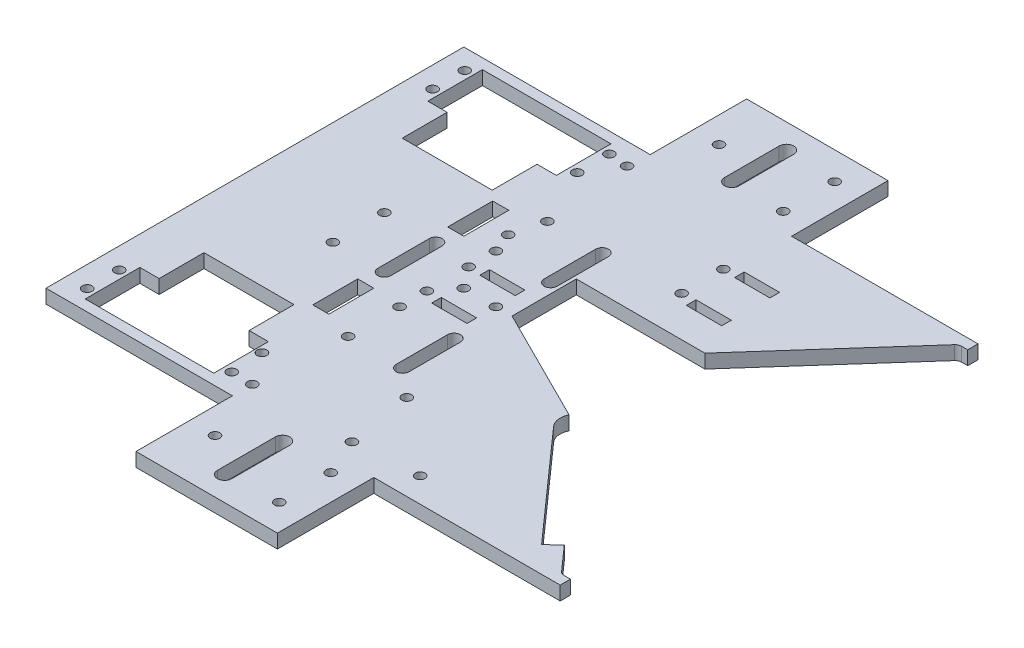
SolidWorks part; units mm, degrees
material "Acrylic (Medium-high impact)"
ref_plane "Front Plane" through (0, 0, 0) normal (0, 0, 1) x (1, 0, 0)
ref_plane "Top Plane" through (0, 0, 0) normal (0, 1, 0) x (1, 0, 0)
ref_plane "Right Plane" through (0, 0, 0) normal (1, 0, 0) x (0, 0, -1)
sketch "Sketch2" plane through (0, 0, 0) normal (0, 1, 0) x (1, 0, 0)
  line L2 (0, 0) -> (0, 65)
  line L3 (0, 65) -> (58, 65)
  line L4 (160, 0) -> (160, 65)
  line L8 (0, 0) -> (160, 0)
  line L9 (102, 65) -> (160, 65)
  line L11 (102, 65) -> (102, 95)
  line L12 (58, 65) -> (58, 95)
  line L13 (58, 95) -> (102, 95)
  dimension "D1" = 65
  dimension "D2" = 160
  dimension "D3" = 44
  dimension "D4" = 30
extrude "Boss-Extrude1" add sketch "Sketch2" along normal blind 4.3
mirror "Mirror1" about plane through (0, 4.3, 0) normal (0, 0, -1) of bodies 101
sketch "Sketch3" plane through (0, 4.3, 0) normal (0, 1, 0) x (1, 0, 0)
  line L0 (160, 61.8) -> (160, -61.8)
  line L1 (120.0126, 20) -> (157.1565, 61.8)
  line L3 (80.0126, 0) -> (80.0126, 20)
  line L4 (80.0126, 20) -> (120.0126, 20)
  line L12 (160, 65) -> (102, 65)
  line L13 (102, 65) -> (102, 95)
  line L15 (102, 95) -> (58, 95)
  line L16 (58, 65) -> (0, 65)
  line L17 (0, 65) -> (0, -65)
  line L18 (0, -65) -> (58, -65)
  line L20 (58, 95) -> (58, 65)
  line L22 (102, -65) -> (160, -65)
  line L23 (160, -65) -> (160, 65)
  line L36 (58, -65) -> (58, -95)
  line L38 (58, -95) -> (102, -95)
  line L39 (58, -95) -> (102, -95)
  line L40 (102, -95) -> (102, -65)
  line L42 (160, -61.8) -> (157.1556, -61.8)
  line L45 (160, 61.8) -> (157.1565, 61.8)
  line L48 (80.0126, 0) -> (120, -20)
  line L49 (120, -20) -> (157.1556, -61.8)
  line M24 (160, -65) -> (160, 65)
  dimension "D2" = 130
  dimension "D3" = 20
  dimension "D4" = 40
  dimension "D1" = 0
extrude "Cut-Extrude1" cut sketch "Sketch3" against normal blind 4.5 contours L48 L49 L1 L4 L3 M24 region at (132.7054, 4.3, -1.1594)
fillet "Fillet1" radius 2 2 edges at (157.1565, 2.15, -61.8) (157.1556, 2.15, 61.8)
ref_axis "Axis1" through (80, 4.3, 95) along (0, 0, -1)
sketch "Sketch4" plane through (0, 4.3, 0) normal (0, 1, 0) x (1, 0, 0)
  line L0 (80, -95) -> (80, 95)
  line L1 (102, -95) -> (58, -95) construction
  line L2 (102, 95) -> (58, 95) construction
ref_plane "Plane2" through (0, 4.3, 0) normal (0, 1, 0) x (1, 0, 0)
sketch "Sketch6" plane through (0, 4.3, 0) normal (0, 1, 0) x (1, 0, 0)
  line L3 (9, -61.8) -> (49, -61.8)
  line L6 (29, -45.8) -> (29, -44.8)
  line L7 (9, -44.8) -> (15, -44.8)
  line L11 (43, -44.8) -> (43, -30.8418)
  line L12 (15, -44.8) -> (15, -30.8418)
  line L13 (15, -30.8418) -> (43, -30.8418)
  line L15 (0, 0) -> (80.0126, 0)
  line L16 (80.0126, 0) -> (120, -20) construction
  line L18 (9, 44.8) -> (15, 44.8)
  line L20 (15, 30.8418) -> (43, 30.8418)
  line L21 (15, 44.8) -> (15, 30.8418)
  line L22 (43, 44.8) -> (43, 30.8418)
  line L25 (15, -45.8) -> (15, -30.8418) construction
  line L27 (9, 61.8) -> (49, 61.8)
  line L30 (4, -61.8) -> (3, -61.8)
  line L31 (0, -61.8) -> (160, -61.8) construction
  line L32 (3, -61.8) -> (4, -61.8)
  line L33 (3, -44.8) -> (3, -62.8) construction
  line L34 (3, -62.8) -> (55, -62.8) construction
  line L35 (55, -44.8) -> (55, -62.8) construction
  line L36 (4, -61.8) -> (54, -61.8) construction
  line L37 (0, 61.8) -> (160, 61.8) construction
  line L38 (54, 61.8) -> (55, 61.8)
  line L39 (54, 61.8) -> (55, 61.8)
  line L40 (43, 44.8) -> (49, 44.8)
  line L41 (4, -45.8) -> (4, -61.8) construction
  line L42 (4, -45.8) -> (54, -45.8) construction
  line L43 (43, -44.8) -> (49, -44.8)
  line L44 (3, -44.8) -> (55, -44.8) construction
  line L45 (29, -45.8) -> (29, -30.8418) construction
  line L46 (43, -45.8) -> (43, -30.8418) construction
  line L47 (54, -45.8) -> (54, -61.8) construction
  line L48 (9, -61.8) -> (49, -61.8)
  line L52 (9, 61.8) -> (9, 44.8)
  line L53 (55, 61.8) -> (54, 61.8)
  line L56 (49, 61.8) -> (49, 44.8)
  line L59 (3, -61.8) -> (4, -61.8)
  line L60 (9, -44.8) -> (9, -61.8)
  line L64 (49, -44.8) -> (49, -61.8)
  dimension "D4" = 1
  dimension "D5" = 14
  dimension "D6" = 14
extrude "Cut-Extrude2" cut sketch "Sketch6" against normal blind 10
sketch "Sketch8" plane through (0, 4.3, 0) normal (0, 1, 0) x (1, 0, 0)
  circle A0 centre (6.5, 58.8) radius 1.5
  circle A1 centre (6.5, 48.8) radius 1.5
  circle A2 centre (51.5, 48.8) radius 1.5
  circle A3 centre (51.5, 58.8) radius 1.5
  circle A4 centre (6.5, -48.7) radius 1.5
  circle A5 centre (6.5, -58.7) radius 1.5
  circle A6 centre (51.5, -58.7) radius 1.5
  circle A7 centre (51, -48.8) radius 1.5
  dimension "D7" = 3
extrude "Cut-Extrude3" cut sketch "Sketch8" against normal blind 10
sketch "Sketch9" plane through (0, 0, 0) normal (0, -1, 0) x (1, 0, 0)
  line L0 (75.75, 69.4) -> (75.75, 87.4)
  line L1 (75.75, -87.4) -> (75.75, -70.4)
  line L2 (80.25, -87.4) -> (80.25, -70.4)
  line L4 (80.25, 69.4) -> (80.25, 87.4)
  circle A0 centre (94, 70.4) radius 1.5
  circle A1 centre (66, 78.4) radius 1.5
  circle A2 centre (66, -78.4) radius 1.5
  circle A3 centre (94, -86.4) radius 1.5
  circle A4 centre (94, 86.4) radius 1.5
  circle A5 centre (94, -70.4) radius 1.5
  arc A6 (75.75, -87.4) -> (80.25, -87.4) centre (78, -87.4) ccw
  arc A7 (80.25, -70.4) -> (75.75, -70.4) centre (78, -70.4) ccw
  arc A10 (75.75, 69.4) -> (80.25, 69.4) centre (78, 69.4) ccw
  arc A12 (80.25, 87.4) -> (75.75, 87.4) centre (78, 87.4) ccw
  dimension "D1" = 3
extrude "Cut-Extrude4" cut sketch "Sketch9" against normal blind 10
sketch "Sketch7" plane through (0, 4.3, 0) normal (0, 1, 0) x (1, 0, 0)
  line L0 (0, 0) -> (80.0126, 0)
  line L1 (0, 65) -> (0, -65) construction
  line L2 (80.0126, 0) -> (80.0126, 20) construction
  line L3 (80, -95) -> (80, 95) construction
  line L4 (64, -9) -> (75, -9)
  line L5 (64, -6) -> (75, -6)
  line L6 (64, -9) -> (64, -6)
  line L7 (75, -9) -> (75, -6)
  line L8 (64, -7.5) -> (75, -7.5)
  line L9 (64, 7.5) -> (75, 7.5)
  line L10 (75, 9) -> (75, 6)
  line L11 (64, 9) -> (64, 6)
  line L12 (64, 6) -> (75, 6)
  line L13 (64, 9) -> (75, 9)
  line L14 (104.2547, 30) -> (115.2547, 30)
  line L15 (104.2547, 33) -> (115.2547, 33)
  line L16 (104.2547, 30) -> (104.2547, 33)
  line L17 (115.2547, 30) -> (115.2547, 33)
  line L20 (115.2547, 48) -> (115.2547, 45)
  line L21 (104.2547, 48) -> (104.2547, 45)
  line L22 (104.2547, 45) -> (115.2547, 45)
  line L23 (104.2547, 48) -> (115.2547, 48)
  line L24 (80.0126, 20) -> (120.0126, 20) construction
  circle A0 centre (60.0126, -6.5) radius 1.5
  circle A1 centre (60.0126, 6.5) radius 1.5
  circle A2 centre (100.2673, 32.5) radius 1.5
  circle A3 centre (100.2673, 45.5) radius 1.5
  point P41 (0, 0)
  point P42 (0, 0)
  point P45 (0, 0)
  point P47 (104.2547, 59.0828)
  dimension "D1" = 3
  dimension "D8" = 3
  dimension "D2" = 6.5
  dimension "D3" = 20
  dimension "D6" = 11
  dimension "D4" = 5
  dimension "D5" = 3
  dimension "D7" = 7.5
  dimension "D9" = 11
  dimension "D10" = 3
  dimension "D11" = 12
  dimension "D12" = 13
  dimension "D13" = 10
  dimension "D14" = 3.9874
  dimension "D15" = 0.5
  dimension "D16" = 0.5
  dimension "D17" = 3.9874
sketch "Sketch10" plane through (0, 4.3, 0) normal (0, 1, 0) x (1, 0, 0)
  line L0 (120, -20) -> (156.5589, -61.1287) construction
  line L1 (123.3218, -23.737) -> (149.8964, -53.6334)
  line L2 (116.263, -23.3218) -> (146.1593, -56.9552)
  line L3 (149.8964, -53.6334) -> (146.1593, -56.9552)
  line L4 (120, -20) -> (156.5589, -61.1287) construction
  line L5 (116.263, -23.3218) -> (152.8218, -64.4505) construction
  arc A0 (123.3218, -23.737) -> (116.263, -23.3218) centre (120, -20) ccw
  dimension "D1" = 5
  dimension "D2" = 45
extrude "Cut-Extrude5" cut sketch "Sketch10" against normal blind 10
sketch "Sketch11" plane through (0, 0, 0) normal (0, -1, 0) x (1, 0, 0)
  line L0 (0, 0) -> (80.0126, 0) construction
  line L1 (80, 95) -> (80, -95) construction
  line L2 (80.0126, 0) -> (0, 0)
  line L4 (75, 31.0313) -> (75, 15.0313)
  line L6 (79, 31.0313) -> (79, 15.0313)
  line L7 (79, -31.0313) -> (79, -15.0313)
  line L8 (75, -31.0313) -> (75, -15.0313)
  circle A0 centre (60, 31) radius 1.5
  circle A1 centre (60, 15) radius 1.5
  arc A2 (75, 31.0313) -> (79, 31.0313) centre (77, 31.0313) cw
  arc A3 (75, 15.0313) -> (79, 15.0313) centre (77, 15.0313) ccw
  arc A4 (75, -15.0313) -> (79, -15.0313) centre (77, -15.0313) cw
  arc A5 (75, -31.0313) -> (79, -31.0313) centre (77, -31.0313) ccw
  circle A6 centre (60, -15) radius 1.5
  circle A7 centre (60, -31) radius 1.5
  dimension "D1" = 3
  dimension "D2" = 16
  dimension "D3" = 15
  dimension "D4" = 20
  dimension "D5" = 15
  dimension "D6" = 4
extrude "Cut-Extrude6" cut sketch "Sketch11" against normal blind 10 contours L4 A3 L6 A2 | L8 A5 L7 A4 | A7 | A0 | A1 | A6 region at (77, 0, 23.0313) region at (77, 0, -23.0313) region at (60, 0, -31)
sketch "Sketch12" plane through (0, 0, 0) normal (0, -1, 0) x (-1, 0, 0)
  line L0 (0, 0) -> (-80.0126, 0) construction
  line L3 (-50.2627, -8) -> (-50.2627, 8)
  line L4 (-50.2627, 0) -> (-46.2627, 0)
  line L5 (-46.2627, -8) -> (-46.2627, 8)
  line L6 (0, 0) -> (-46.2627, 0)
  line L7 (0, 65) -> (0, -65) construction
  line L8 (-160, -61.8) -> (0, -61.8) construction
  line L9 (-80.0126, 0) -> (-50.2627, 0)
  line L10 (-80.0126, 0) -> (-115.5281, -17.7634) construction
  line L11 (-80.0126, 0) -> (-80.0126, 20) construction
  line L12 (-58, -65) -> (0, -65) construction
  line L13 (-58, 65) -> (0, 65) construction
  circle A0 centre (-32.2627, -8) radius 1.5
  circle A1 centre (-32.2627, 8) radius 1.5
  arc A2 (-46.2627, 8) -> (-50.2627, 8) centre (-48.2627, 8) ccw
  arc A3 (-50.2627, -8) -> (-46.2627, -8) centre (-48.2627, -8) ccw
  circle A5 centre (-32.2627, -8) radius 1.5 construction
  circle A6 centre (-32.2627, 8) radius 1.5 construction
  dimension "D1" = 3
  dimension "D8" = 8
  dimension "D9" = 8
  dimension "D2" = 8
  dimension "D3" = 14
  dimension "D4" = 4
  dimension "D5" = 61.8
  dimension "D6" = 65
  dimension "D7" = 65
extrude "Cut-Extrude7" cut sketch "Sketch12" against normal blind 10 contours A3 L5 L4 L3 | L4 L5 A2 L3 | A0 | A1 region at (48.2627, 0, 4.7958) region at (48.2627, 0, -4.7958) region at (32.2627, 0, 8) region at (32.2627, 0, -8)
extrude "Cut-Extrude8" cut sketch "Sketch7" against normal blind 9 contours A0 | L4 L7 L5 L6 | L12 L10 L13 L11 | A1 | L23 L20 L22 L21 | L15 L17 L14 L16 | A3 | A2
sketch "Sketch13" plane through (0, 4.3, 0) normal (0, 1, 0) x (1, 0, 0)
  line L0 (80.0126, 0) -> (59.0194, 0)
  line L1 (80, -95) -> (80, 95) construction
  circle A0 centre (65, 0) radius 1.5
  circle A1 centre (75, 0) radius 1.5
  dimension "D2" = 3
  dimension "D3" = 5
  dimension "D1" = 10
extrude "Cut-Extrude9" cut sketch "Sketch13" against normal blind 10 contours L0 A0 | L0 A0 | L0 A1 | L0 A1 region at (75, 4.3, 0.6366) region at (75, 4.3, -0.6366) region at (65, 4.3, 0.6366) region at (65, 4.3, -0.6366)
sketch "Sketch14" plane through (0, 4.3, 0) normal (0, 1, 0) x (1, 0, 0)
  circle A0 centre (57.5, 58.3) radius 1.5
  circle A2 centre (57.5, 21.3) radius 1.5
  circle A3 centre (85.5653, -38.3098) radius 1.5
  circle A4 centre (108.7541, -57.3434) radius 1.5
  dimension "D1" = 3
  dimension "D2" = 3
extrude "Cut-Extrude10" cut sketch "Sketch14" against normal blind 10
sketch "Sketch15" plane through (0, 4.3, 0) normal (0, 1, 0) x (1, 0, 0)
  line L1 (46, 28) -> (51, 28)
  line L2 (46, 28) -> (46, 14)
  line L3 (46, 14) -> (51, 14)
  line L4 (51, 28) -> (51, 14)
  line L6 (0, 65) -> (0, -65) construction
  line L7 (80.0126, 0) -> (53.7017, 0)
  line L8 (46, -14) -> (51, -14)
  line L9 (51, -28) -> (51, -14)
  line L10 (46, -28) -> (51, -28)
  line L11 (46, -28) -> (46, -14)
  arc A0 (50.2627, 8) -> (46.2627, 8) centre (48.2627, 8) ccw construction
  arc A1 (46.2627, -8) -> (50.2627, -8) centre (48.2627, -8) ccw construction
  dimension "D1" = 46
  dimension "D2" = 5
  dimension "D3" = 14
  dimension "D4" = 14
  dimension "D5" = 14
  dimension "D6" = 6
  dimension "D7" = 6
extrude "Cut-Extrude11" cut sketch "Sketch15" against normal blind 10 contours L4 L1 L2 L3 | L11 L10 L9 L8 region at (48.5, 4.3, -21) region at (48.5, 4.3, 21)
sketch "Sketch16" plane through (0, 4.3, 0) normal (0, 1, 0) x (1, 0, 0)
  circle A0 centre (89, -58.8) radius 1.5
  circle A1 centre (58, -58.8) radius 1.5
  dimension "D1" = 3
extrude "Cut-Extrude12" cut sketch "Sketch16" against normal blind 10
ref_plane "Plane3" through (44.2426, 0, 0) normal (1, 0, 0) x (0, 0, -1)
sketch "Sketch17" plane through (44.2426, 0, 0) normal (1, 0, 0) x (0, 0, -1)
  line L4 (0, 0) -> (20, 0)
  line L5 (20, 0) -> (20, 4.3)
  line L6 (20, 4.3) -> (0, 4.3)
  line L7 (0, 4.3) -> (0, 0)
  line L8 (0, 0) -> (20, 0)
  line L9 (20, 0) -> (20, 4.3)
  line L10 (20, 4.3) -> (0, 4.3)
  line L11 (0, 4.3) -> (0, 0)
  circle A0 centre (-2.83, 16.28) radius 0.5
  point P6 (0, 2.15)
  dimension "D4" = 1
  dimension "D2" = 2.83
  dimension "D3" = 14.13
  dimension "D1" = 0
